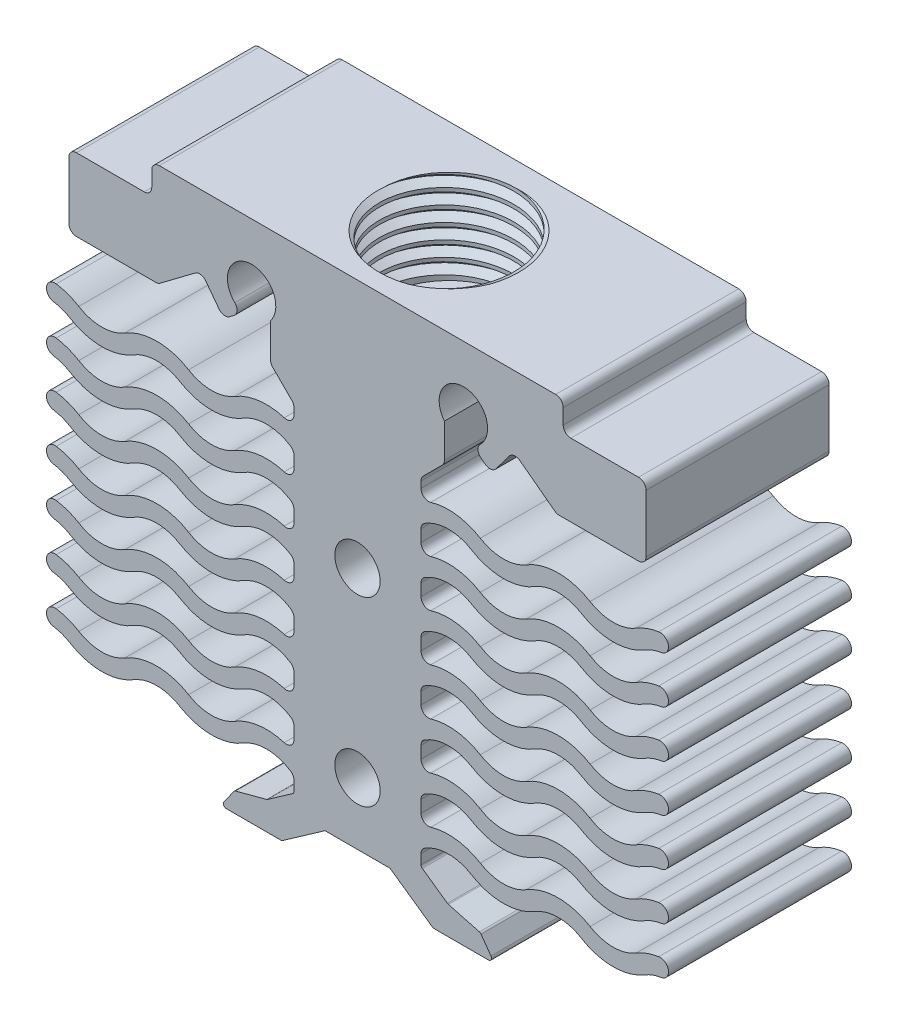
SolidWorks part; units mm, degrees
material "1060 Сплав"
ref_plane "Front" through (0, 0, 0) normal (0, 0, 1) x (1, 0, 0)
ref_plane "Top" through (0, 0, 0) normal (0, 1, 0) x (1, 0, 0)
ref_plane "Right" through (0, 0, 0) normal (1, 0, 0) x (0, 0, -1)
sketch "body sketch" plane through (0, 0, 0) normal (0, 0, 1) x (1, 0, 0)
  line L0 (-13.6, 0) -> (13.6, 0)
  line L1 (-43.5493, -8.3555) -> (-2.5493, -8.3555) construction
  line L2 (13.6, 0) -> (13.6, -2)
  line L3 (13.6, -2) -> (19.08, -2)
  line L4 (19.08, -2) -> (19.08, -6.8)
  line L5 (19.08, -6.8) -> (13.1746, -6.8)
  line L6 (13.1746, -6.8) -> (10.333, -4.664)
  line L7 (10.333, -4.664) -> (8.8558, -6.6292)
  line L8 (8.8558, -6.6292) -> (7.5807, -5.6707)
  line L9 (7.5807, -5.6707) -> (8.4124, -4.5643)
  line L10 (8.4124, -4.5643) -> (6.9397, -3.4573)
  line L11 (6.9397, -3.4573) -> (5.75, -5.04)
  line L12 (5.75, -5.04) -> (5.75, -7.648)
  line L13 (5.75, -7.648) -> (4.2, -9.198)
  line L14 (4.2, -9.198) -> (4.2, -31.483)
  line L15 (4.2, -31.483) -> (5.976, -32.7293)
  line L16 (5.976, -32.7293) -> (8.1274, -33.3042)
  line L17 (8.1274, -33.3042) -> (9.05, -34.6)
  line L18 (9.05, -34.6) -> (5, -34.6)
  line L19 (5, -34.6) -> (2.15, -32.6)
  line L20 (2.15, -32.6) -> (-2.15, -32.6)
  line L21 (-19.5012, -3.9393) -> (18.6487, -3.8974) construction
  line L22 (0, -32.6) -> (0, 0) construction
  line L23 (-5, -34.6) -> (-2.15, -32.6)
  line L24 (-9.05, -34.6) -> (-5, -34.6)
  line L25 (-8.1274, -33.3042) -> (-9.05, -34.6)
  line L26 (-5.976, -32.7293) -> (-8.1274, -33.3042)
  line L27 (-4.2, -31.483) -> (-5.976, -32.7293)
  line L28 (-4.2, -9.198) -> (-4.2, -31.483)
  line L29 (-5.75, -7.648) -> (-4.2, -9.198)
  line L30 (-5.75, -5.04) -> (-5.75, -7.648)
  line L31 (-6.9397, -3.4573) -> (-5.75, -5.04)
  line L32 (-8.4124, -4.5643) -> (-6.9397, -3.4573)
  line L33 (-7.5807, -5.6707) -> (-8.4124, -4.5643)
  line L34 (-8.8558, -6.6292) -> (-7.5807, -5.6707)
  line L35 (-10.333, -4.664) -> (-8.8558, -6.6292)
  line L36 (-13.1746, -6.8) -> (-10.333, -4.664)
  line L37 (-19.08, -6.8) -> (-13.1746, -6.8)
  line L38 (-19.08, -2) -> (-19.08, -6.8)
  line L39 (-13.6, -2) -> (-19.08, -2)
  line L40 (-13.6, 0) -> (-13.6, -2)
  dimension "D1" = 13.6
  dimension "D2" = 19.08
  dimension "D3" = 2
  dimension "D4" = 4.8
  dimension "D5" = 9.05
  dimension "D6" = 4.2
  dimension "D7" = 5
  dimension "D8" = 45
  dimension "D9" = 2
  dimension "D10" = 34.6
  dimension "D11" = 5.75
  dimension "D12" = 32.6
  dimension "D13" = 41
  dimension "D14" = 38.15
  dimension "D15" = 2.15
sketch "mount sketch" plane through (0, 0, 0) normal (0, 0, 1) x (1, 0, 0)
  circle A0 centre (-7, -4.2) radius 1.6
  circle A1 centre (7, -4.2) radius 1.6
  dimension "D3" = 3.2
  dimension "D1" = 7
  dimension "D2" = 4.2
  dimension "D4" = 2
sketch "blades sketch" plane through (0, 0, 0) normal (0, 0, 1) x (1, 0, 0)
  line L0 (-19.0597, -4.4032) -> (19.0903, -4.4032) construction
  line L1 (4.2, -9.198) -> (4.2, -31.483) construction
  arc A0 (7.8282, -11.2) -> (11.4563, -11.2) centre (9.6423, -8.2068) ccw construction
  arc A1 (15.0845, -11.2) -> (18.7127, -11.2) centre (16.8986, -8.2068) ccw construction
  arc A2 (4.2, -11.2) -> (7.8282, -11.2) centre (6.0141, -14.1932) cw construction
  arc A3 (11.4563, -11.2) -> (15.0845, -11.2) centre (13.2704, -14.1932) cw construction
  arc A4 (18.7127, -11.2) -> (20, -10.733) centre (20.5268, -14.1932) cw construction
  arc A5 (4.4903, -11.6789) -> (7.5379, -11.6789) centre (6.0141, -14.1932) cw
  arc A6 (7.5379, -11.6789) -> (11.7466, -11.6789) centre (9.6423, -8.2068) ccw
  arc A7 (11.7466, -11.6789) -> (14.7943, -11.6789) centre (13.2704, -14.1932) cw
  arc A8 (14.7943, -11.6789) -> (19.0029, -11.6789) centre (16.8986, -8.2068) ccw
  arc A9 (19.0029, -11.6789) -> (20.0843, -11.2867) centre (20.5268, -14.1932) cw
  arc A10 (3.9097, -10.7211) -> (8.1184, -10.7211) centre (6.0141, -14.1932) cw
  arc A11 (8.1184, -10.7211) -> (11.1661, -10.7211) centre (9.6423, -8.2068) ccw
  arc A12 (11.1661, -10.7211) -> (15.3748, -10.7211) centre (13.2704, -14.1932) cw
  arc A13 (15.3748, -10.7211) -> (18.4224, -10.7211) centre (16.8986, -8.2068) ccw
  arc A14 (18.4224, -10.7211) -> (19.9157, -10.1794) centre (20.5268, -14.1932) cw
  arc A15 (19.9157, -10.1794) -> (20.0843, -11.2867) centre (20, -10.733) cw
  arc A16 (4.4903, -11.6789) -> (3.9097, -10.7211) centre (4.2, -11.2) cw
  arc A89 (3.9097, -10.7211) -> (8.1184, -10.7211) centre (6.0141, -14.1932) cw construction
  arc A90 (19.0029, -11.6789) -> (20.0843, -11.2867) centre (20.5268, -14.1932) cw construction
  point P3 (0, 0)
  point P18 (0, 0)
  dimension "D2" = 3.5
  dimension "D1" = 11.2
  dimension "D3" = 20
  dimension "D4" = 0.56
  dimension "D5" = 0.56
extrude "body " add sketch "body sketch" against normal blind 6.05 and the other way blind 6.05
extrude "mount holes" cut sketch "mount sketch" against normal through all both and the other way through all
extrude "blade" add sketch "blades sketch" against normal blind 6.05 and the other way blind 6.05
pattern_linear "blades array" count 7 spacing 3.1 along (0, -1, 0) of "blade"
mirror "mirror" about plane through (0, 0, 0) normal (1, 0, 0) of "blades array"
sketch "thermobreak sketch" plane through (0, 0, 0) normal (0, 1, 0) x (1, 0, 0)
  circle A0 centre (0, 0) radius 3.05
  dimension "D1" = 6.1
sketch "fiting sketch" plane through (0, 0, 0) normal (0, 1, 0) x (1, 0, 0)
  circle A1 centre (0, 0) radius 4.45
  dimension "D2" = 8.9
extrude "fiting thtead" cut sketch "fiting sketch" against normal blind 6.2
extrude "thermobreak hole" cut sketch "thermobreak sketch" against normal up to next
sketch "retaining sketch" plane through (0, 0, 0) normal (0, 0, 1) x (1, 0, 0)
  circle A0 centre (0, -16.5) radius 1.5
  circle A1 centre (0, -28.5) radius 1.5
  dimension "D2" = 3
  dimension "D1" = 16.5
  dimension "D3" = 2
extrude "retaining holes" cut sketch "retaining sketch" along normal through all
sketch "heater mount sketch" plane through (0, -34.6, 0) normal (0, -1, 0) x (1, 0, 0)
  circle A0 centre (-7, 0) radius 1
  circle A1 centre (7, 0) radius 1
  dimension "D1" = 2
  dimension "D2" = 7
  dimension "D3" = 2
fillet "rounding1" radius 0.5 20 edges at (-4.2, -9.198, 0) (-5.75, -7.648, 0) (-8.8558, -6.6292, 0) (-10.333, -4.664, 0) (-13.1746, -6.8, 0) (-19.08, -6.8, 0) (-19.08, -2, 0) (-13.6, -2, 0) (-13.6, 0, 0) (-7.5983, -5.6839, 0) (13.6, 0, 0) (13.6, -2, 0) (19.08, -2, 0) (19.08, -6.8, 0) (13.1746, -6.8, 0) (10.333, -4.664, 0) (8.8558, -6.6292, 0) (7.5983, -5.6839, 0) (4.2, -9.198, 0) (5.75, -7.648, 0)
fillet "rounding2" radius 0.5 28 edges at (-4.2, -10.561, 0) (-4.2, -13.661, 0) (-4.2, -16.761, 0) (-4.2, -19.861, 0) (-4.2, -22.961, 0) (-4.2, -26.061, 0) (-4.2, -29.161, 0) (4.2, -29.161, 0) (4.2, -26.061, 0) (4.2, -22.961, 0) (4.2, -19.861, 0) (4.2, -16.761, 0) (4.2, -13.661, 0) (4.2, -10.561, 0) (-4.2, -11.76, 0) (-4.2, -14.86, 0) (-4.2, -17.96, 0) (-4.2, -21.06, 0) (-4.2, -24.16, 0) (-4.2, -27.26, 0) (-4.2, -30.36, 0) (4.2, -30.36, 0) (4.2, -27.26, 0) (4.2, -24.16, 0) (4.2, -21.06, 0) (4.2, -17.96, 0) (4.2, -14.86, 0) (4.2, -11.76, 0)
fillet "rounding3" radius 0.2 10 edges at (-9.05, -34.6, 0) (9.05, -34.6, 0) (-4.2, -31.483, 0) (4.2, -31.483, 0) (5.976, -32.7293, 0) (8.1274, -33.3042, 0) (5, -34.6, 0) (-5, -34.6, 0) (-5.976, -32.7293, 0) (-8.1274, -33.3042, 0)
extrude "heater mount holes" cut sketch "heater mount sketch" against normal up to next
thread "thread" pitch 1 method cut trim with start face yes trim with end face yes profile "thread profile" start angle 0, offset 1, length 7, pitch 1, diameter 8.9
ref_plane "Плоскость1" through (-4.45, 1, 0) normal (0, 0, 1) x (-1, 0, 0)
sketch "thread profile" plane through (-4.45, 1, 0) normal (0, 0, 1) x (-1, 0, 0)
  line L0 (0, 0) -> (0, 1) construction
  line L1 (0, 0) -> (0.5413, 0.3125)
  line L2 (0.5413, 0.3125) -> (0.5413, 0.4375)
  line L3 (0.5413, 0.4375) -> (0, 0.75)
  line L4 (0.5413, 0.375) -> (0, 0.375) construction
  line L11 (0, 0) -> (0, 0.75)
  point P2 (0, 0)
  dimension "Pitch" = 1
  dimension "Profile_Angle" = 60
  dimension "Profile_Land" = 0.125
  dimension "Profile_Height" = 0.5413
